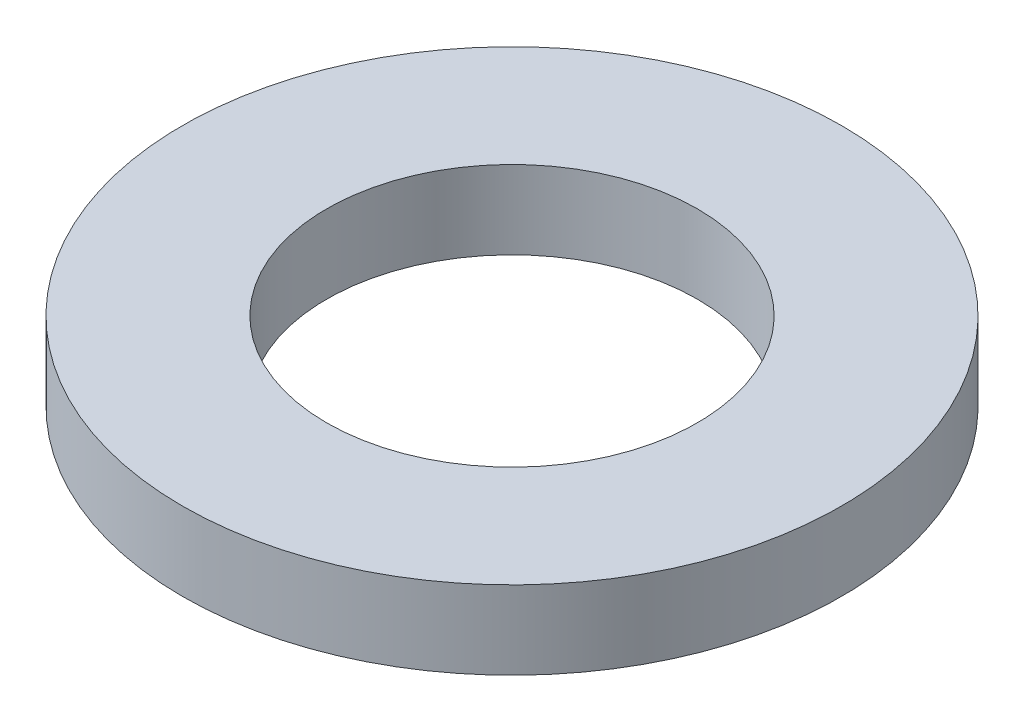
SolidWorks part; units mm, degrees
ref_plane "Front Plane" through (0, 0, 0) normal (0, 0, 1) x (1, 0, 0)
ref_plane "Top Plane" through (0, 0, 0) normal (0, 1, 0) x (1, 0, 0)
ref_plane "Right Plane" through (0, 0, 0) normal (1, 0, 0) x (0, 0, -1)
sketch "Sketch1" plane through (0, 0, 0) normal (0, 1, 0) x (1, 0, 0)
  circle A0 centre (0, 0) radius 80
  dimension "FLANGE_OD" = 160
extrude "Boss-Extrude1" add sketch "Sketch1" along normal blind 19
sketch "Sketch2" plane through (0, 0, 0) normal (0, 1, 0) x (1, 0, 0)
  circle A0 centre (0, 0) radius 45
  dimension "BORE_D" = 90
extrude "Cut-Extrude1" cut sketch "Sketch2" along normal through all
sketch "Sketch3" plane through (0, 19, 0) normal (0, 1, 0) x (1, 0, 0)
  circle A0 centre (0, 0) radius 31.7846 construction
  circle A1 centre (-31.7846, 0) radius 4.0369
  dimension "BOLT_D" = 8.0739
  dimension "BOLT_PCD" = 63.5692
extrude "Cut-Extrude2" cut sketch "Sketch3" against normal blind 16.5444 rebuild error yes
pattern_circular "CirPattern1" count 4 over 360 rebuild error yes
